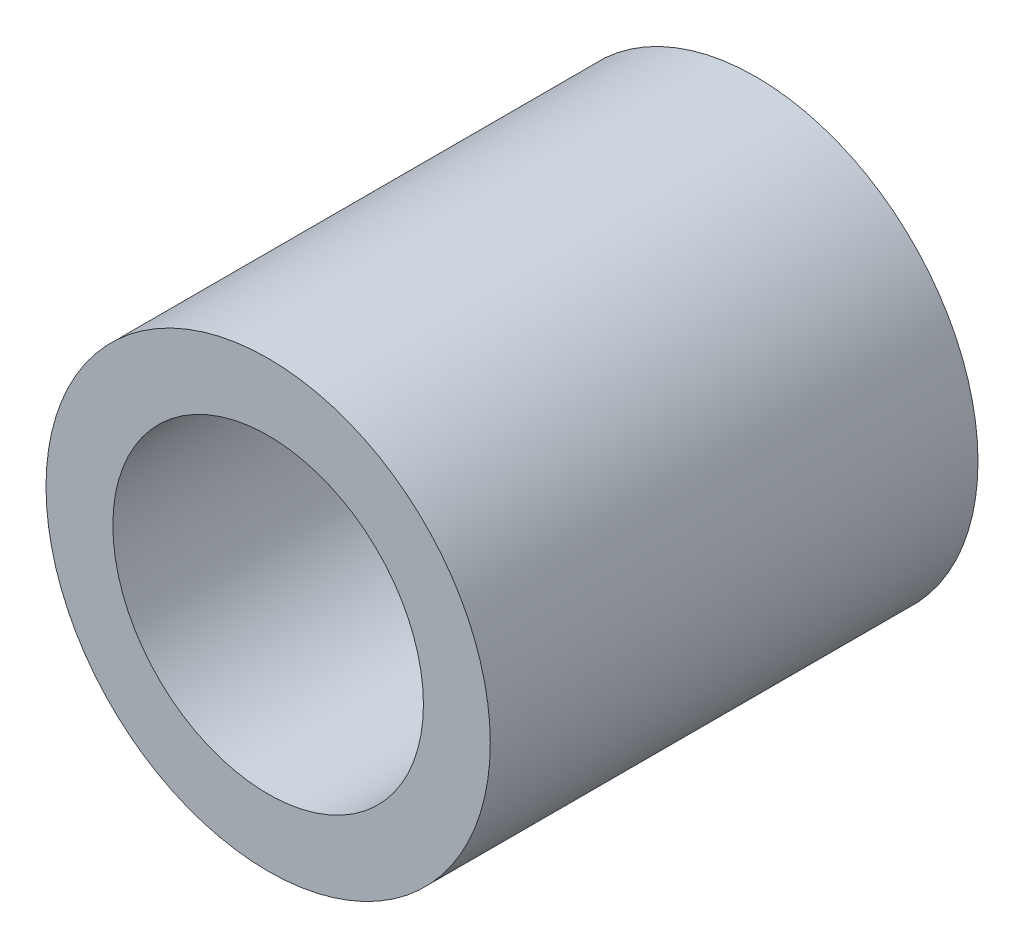
SolidWorks part; units mm, degrees
material "Tin Bearing Bronze"
ref_plane "Front Plane" through (0, 0, 0) normal (0, 0, 1) x (1, 0, 0)
ref_plane "Top Plane" through (0, 0, 0) normal (0, 1, 0) x (1, 0, 0)
ref_plane "Right Plane" through (0, 0, 0) normal (1, 0, 0) x (0, 0, -1)
sketch "Sketch1" plane through (0, 0, 0) normal (0, 0, 1) x (1, 0, 0)
  circle A0 centre (0, 0) radius 10.02
  circle A1 centre (0, 0) radius 7.005
  dimension "ID" = 14.01
  dimension "OD" = 20.04
extrude "Boss-Extrude1" add sketch "Sketch1" along normal mid plane 22
sketch "Sketch2" plane through (0, 0, 0) normal (1, 0, 0) x (0, 0, -1)
  line L0 (-11, 10.02) -> (11, 10.02)
  line L1 (-11, 0) -> (11, 0) construction
  line L2 (-11, 10.02) -> (-11, -10.02) construction
  line L3 (11, -10.02) -> (11, 10.02) construction
  dimension "D1" = 20.04
  dimension "D2" = 22
ref_axis "Center Axis 1" through (0, 0, 4.4) along (0, 0, -1)
ref_plane "Contact Plane 1" through (0, 0, 11) normal (0, 0, 1) x (1, 0, 0)
ref_plane "Contact Plane 2" through (0, 0, -11) normal (0, 0, -1) x (-1, 0, 0)
equation "\"D1@Sketch2\"=\"OD@Sketch1\""
